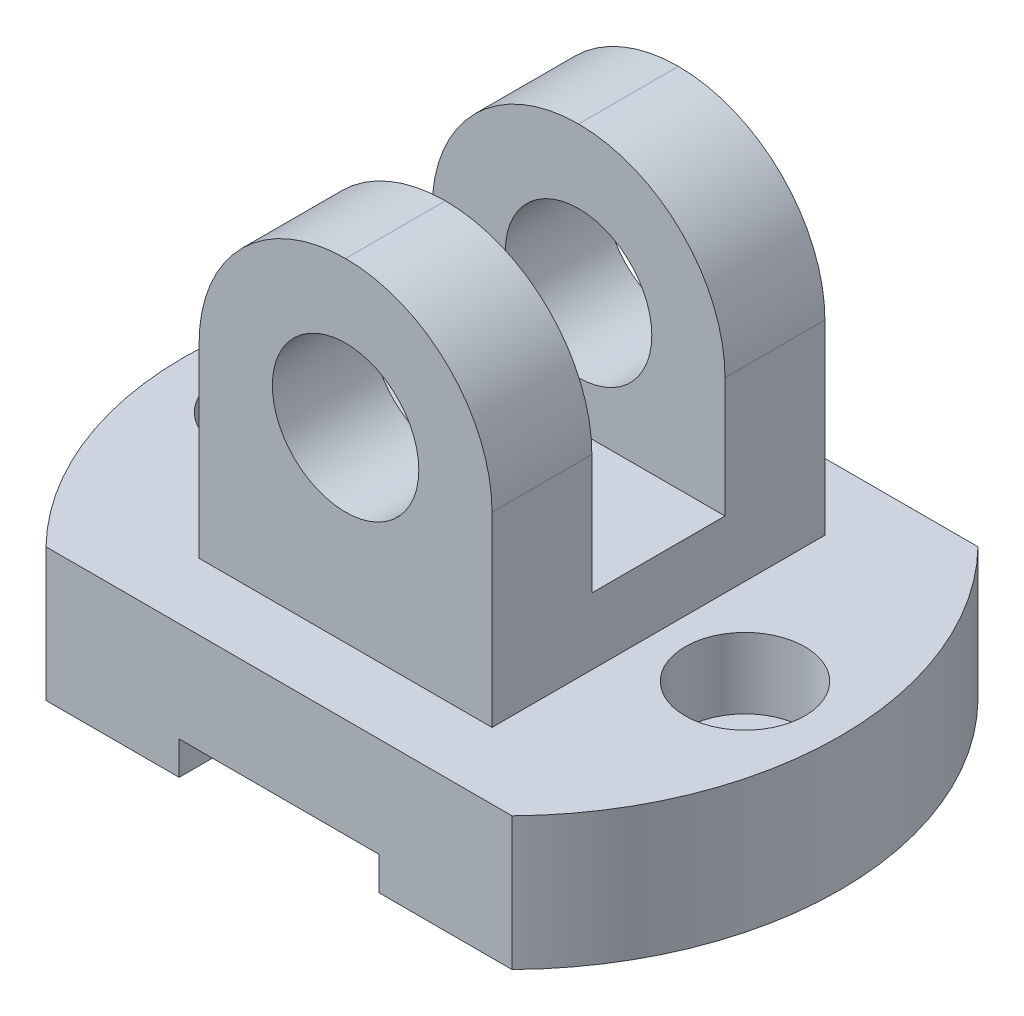
SolidWorks part; units mm, degrees
ref_plane "Piano frontale" through (0, 0, 0) normal (0, 0, 1) x (1, 0, 0)
ref_plane "Piano superiore" through (0, 0, 0) normal (0, 1, 0) x (1, 0, 0)
ref_plane "Piano destro" through (0, 0, 0) normal (1, 0, 0) x (0, 0, -1)
sketch "Schizzo1" plane through (0, 0, 0) normal (1, 0, 0) x (0, 0, -1)
  line L0 (0, 45.6236) -> (0, -20.3861) construction
  line L1 (10, 30) -> (-10, 30)
  line L2 (-10, 30) -> (-10, 70)
  line L3 (-10, 70) -> (-25, 70)
  line L4 (-25, 70) -> (-25, 20)
  line L5 (-25, 20) -> (-35, 20)
  line L6 (-35, 20) -> (-35, 0)
  line L7 (-35, 0) -> (35, 0)
  line L8 (-25, 20) -> (25, 20)
  line L9 (35, 20) -> (35, 0)
  line L10 (25, 20) -> (35, 20)
  line L11 (25, 70) -> (25, 20)
  line L12 (10, 70) -> (25, 70)
  line L13 (10, 30) -> (10, 70)
  point P3 (-17.2754, 37.8352)
  point P13 (0, 0)
  point P15 (0, 20)
  point P18 (0, 30)
  point P19 (0, 45.6236)
  dimension "D1" = 20
  dimension "D2" = 30
  dimension "D3" = 70
  dimension "D4" = 20
  dimension "D5" = 50
  dimension "D6" = 70
extrude "Estrusione-Estrusione1" add sketch "Schizzo1" along normal mid plane 70 contours L0 L8 L5 L6 L7 | L8 L0 L7 L9 L10 region at (0, 10, -17.5) region at (0, 10, 17.5)
extrude "Estrusione-Estrusione2" add sketch "Schizzo1<3>" along normal mid plane 44 contours L0 L1 L2 L3 L4 L8 | L1 L0 L8 L11 L12 L13 region at (0, 42.6471, -16.0294) region at (0, 42.6471, 16.0294)
sketch "Schizzo1<3>" plane through (0, 0, 0) normal (1, 0, 0) x (0, 0, -1) same geometry as "Schizzo1"
sketch "Schizzo2" plane through (0, 0, 0) normal (0, -1, 0) x (1, 0, 0)
  line L0 (-35, 35) -> (-35, -35)
  line L1 (35, 35) -> (35, -35)
  arc A1 (-35, 35) -> (-35, -35) centre (0.7071, 0) ccw
  arc A2 (35, 35) -> (35, -35) centre (-0.7071, 0) cw
  dimension "D1" = 50
  dimension "D2" = 50
extrude "Estrusione-Estrusione3" add sketch "Schizzo2" against normal blind 20
sketch "Schizzo3" plane through (0, 0, -35) normal (0, 0, -1) x (-1, 0, 0)
  line L0 (0, 0) -> (0, 27.5102) construction
  line L1 (-15, 0) -> (-15, 5)
  line L2 (-35, 0) -> (35, 0) construction
  line L3 (-15, 5) -> (15, 5)
  line L4 (15, 0) -> (15, 5)
  point P9 (0, 5)
  dimension "D1" = 30
  dimension "D2" = 5
extrude "Taglio-Estrusione1" cut sketch "Schizzo3" against normal through all and the other way through all
hole_wizard "Foro Ø22.0 (22)-1" positions "Schizzo4" profile "Schizzo5" hole size "Ø22.0" standard "ISO" end condition through all
sketch "Schizzo4" plane through (0, 0, 25) normal (0, 0, 1) x (1, 0, 0)
  line L0 (-22, 48) -> (22, 48) construction
  line L1 (-22, 70) -> (-22, 20) construction
  line L2 (22, 70) -> (22, 20) construction
  line L4 (0, 0) -> (0, 70) construction
  line L6 (22, 70) -> (-22, 70) construction
  line L7 (-15, 0) -> (-35, 0) construction
  point P17 (0, 48)
  point P20 (0, 0)
  point P21 (0, 0)
  dimension "D1" = 48
sketch "Schizzo5" plane through (0, 48, 25) normal (1, 0, 0) x (0, -1, 0)
  line L0 (0, 0) -> (0, 60)
  line L1 (0, 60) -> (11, 60)
  line L2 (11, 60) -> (11, 0)
  line L5 (11, 0) -> (0, 0)
  line L11 (0, -6.35) -> (0, 107.95) construction
  dimension "Thru Hole Dia." = 22
  dimension "Thru Hole Depth" = 60
hole_wizard "Foro lamato per Vite M10 a testa cilindrica-1" positions "Schizzo6" profile "Schizzo7" counterbore size "M10" standard "ISO" end condition up to next
sketch "Schizzo6" plane through (0, 20, 0) normal (0, 1, 0) x (1, 0, 0)
  line L0 (0, 35) -> (0, -35) construction
  line L1 (35, 35) -> (-35, 35) construction
  line L2 (35, -35) -> (-35, -35) construction
  line L4 (0, 0) -> (-49.2929, 0) construction
  line L5 (-35, -35) -> (-35, 35) construction
  arc A0 (-35, 35) -> (-35, -35) centre (0.7071, 0) ccw construction
  point P24 (-35, 0)
  point P27 (0, 0)
  point P28 (35, 0)
sketch "Schizzo7" plane through (35, 20, 0) normal (1, 0, 0) x (0, 0, 1)
  line L0 (0, 0) -> (0, 20)
  line L1 (0, 20) -> (5.5, 20)
  line L3 (5.5, 20) -> (5.5, 10.6)
  line L4 (5.5, 10.6) -> (9, 10.6)
  line L5 (9, 10.6) -> (9, 0)
  line L7 (9, 0) -> (0, 0)
  line L11 (0, -6.35) -> (0, 107.95) construction
  dimension "Thru Hole Dia." = 11
  dimension "Thru Hole Depth" = 20
  dimension "C'Bore Dia." = 18
  dimension "C'Bore Depth" = 10.6
hole_wizard "Foro Ø16.0 (16)-1" positions "Schizzo8" profile "Schizzo9" hole size "Ø16.0" standard "ISO" end condition up to next
sketch "Schizzo8" plane through (0, 30, 0) normal (0, 1, 0) x (1, 0, 0)
  point P0 (0, 0)
sketch "Schizzo9" plane through (0, 30, 0) normal (1, 0, 0) x (0, 0, 1)
  line L0 (0, 0) -> (0, 25)
  line L1 (0, 25) -> (8, 25)
  line L2 (8, 25) -> (8, 0)
  line L5 (8, 0) -> (0, 0)
  line L11 (0, -6.35) -> (0, 107.95) construction
  dimension "Thru Hole Dia." = 16
  dimension "Thru Hole Depth" = 25
fillet "Raccordo1" radius 22 4 edges at (-22, 70, 17.5) (22, 70, 17.5) (22, 70, -17.5) (-22, 70, -17.5)
sketch "Schizzo10" plane through (0, 0, 0) normal (0, 1, 0) x (1, 0, 0)
  line L0 (0, 0) -> (0, 37.864)
